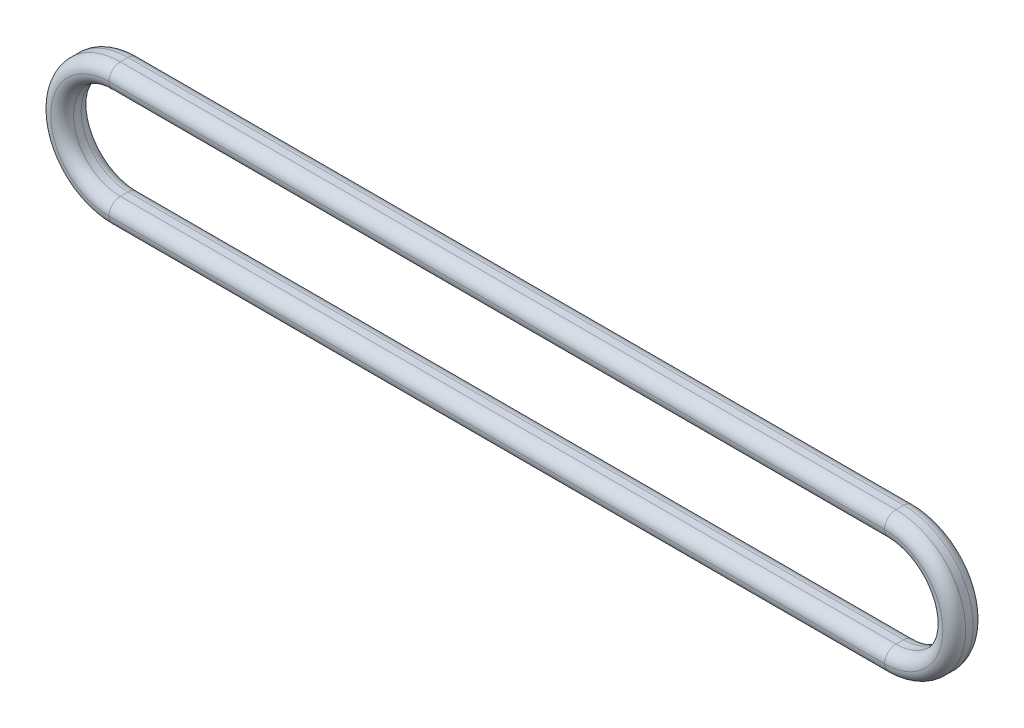
SolidWorks part; units mm, degrees
ref_plane "Front Plane" through (0, 0, 0) normal (0, 0, 1) x (1, 0, 0)
ref_plane "Top Plane" through (0, 0, 0) normal (0, 1, 0) x (1, 0, 0)
ref_plane "Right Plane" through (0, 0, 0) normal (1, 0, 0) x (0, 0, -1)
sketch "Sketch1" plane through (0, 0, 0) normal (0, 0, 1) x (1, 0, 0)
  line L0 (0, 0) -> (-361.95, 0) construction
  line L1 (0, -21.844) -> (-361.95, -21.844)
  line L2 (0, 21.844) -> (-361.95, 21.844)
  line L3 (-361.95, 0) -> (0, 0) construction
  line L4 (-361.95, 32.512) -> (0, 32.512)
  line L5 (-361.95, -32.512) -> (0, -32.512)
  arc A0 (0, -21.844) -> (0, 21.844) centre (0, 0) ccw
  arc A1 (-361.95, 21.844) -> (-361.95, -21.844) centre (-361.95, 0) ccw
  arc A2 (-361.95, 32.512) -> (-361.95, -32.512) centre (-361.95, 0) ccw
  arc A3 (0, -32.512) -> (0, 32.512) centre (0, 0) ccw
  point P3 (-180.975, 0)
  point P10 (-180.975, 0)
  dimension "D2" = 21.844
  dimension "D3" = 32.512
  dimension "D1" = 361.95
extrude "Boss-Extrude1" add sketch "Sketch1" along normal blind 14.224
fillet "Fillet1" radius 5.334 16 edges at (-180.975, -21.844, 0) (-383.794, 0, 0) (-180.975, 21.844, 0) (21.844, 0, 0) (-180.975, -32.512, 0) (32.512, 0, 0) (-180.975, 32.512, 0) (-394.462, 0, 0) (-383.794, 0, 14.224) (-180.975, -21.844, 14.224) (21.844, 0, 14.224) (-180.975, 21.844, 14.224) (-180.975, 32.512, 14.224) (32.512, 0, 14.224) (-180.975, -32.512, 14.224) (-394.462, 0, 14.224)
